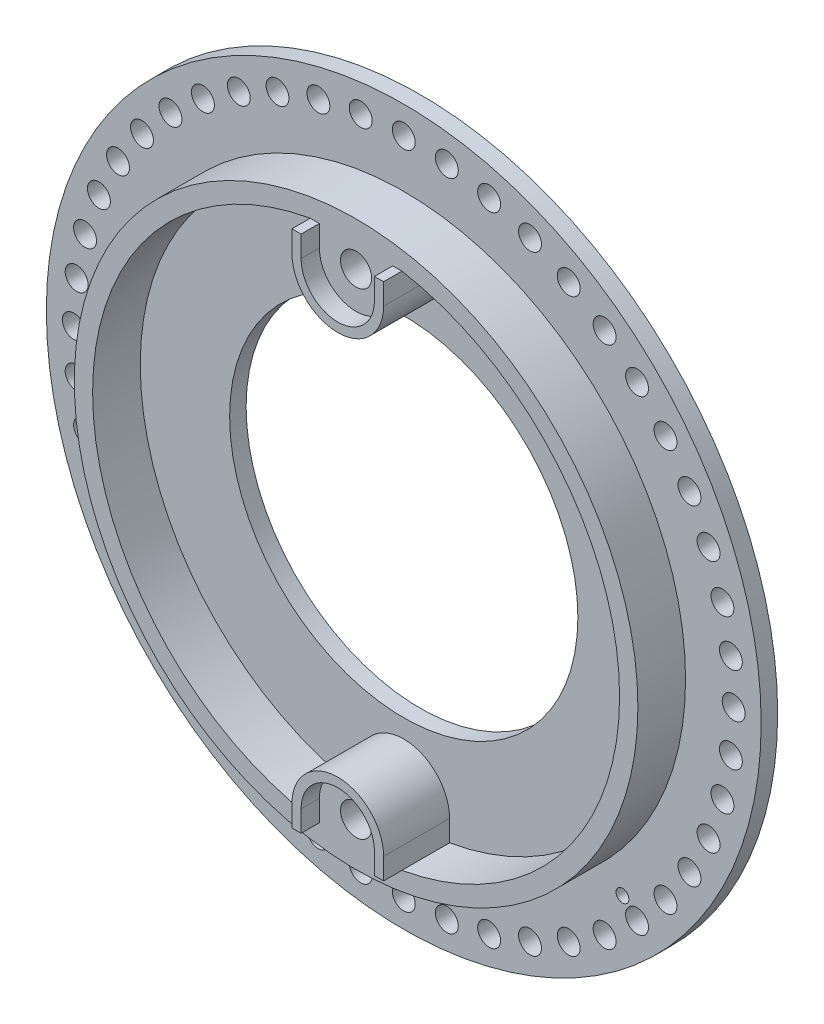
SolidWorks part; units mm, degrees
ref_plane "Front Plane" through (0, 0, 0) normal (0, 0, 1) x (1, 0, 0)
ref_plane "Top Plane" through (0, 0, 0) normal (0, 1, 0) x (1, 0, 0)
ref_plane "Right Plane" through (0, 0, 0) normal (1, 0, 0) x (0, 0, -1)
sketch "Sketch1" plane through (0, 0, 0) normal (0, 0, 1) x (1, 0, 0)
  circle A0 centre (0, 0) radius 39
  dimension "D1" = 78
extrude "Boss-Extrude1" add sketch "Sketch1" along normal blind 1.8
sketch "Sketch3" plane through (0, 0, 1.8) normal (0, 0, 1) x (1, 0, 0)
  line L0 (-5, 26) -> (-5, 28.3119)
  line L1 (5, 26) -> (5, 28.3119)
  line L2 (5, -26) -> (5, -28.3119)
  line L3 (-5, -26) -> (-5, -28.3119)
  circle A0 centre (0, 0) radius 30.75
  arc A1 (-5, 28.3119) -> (-5, -28.3119) centre (0, 0) ccw
  arc A2 (-5, 26) -> (5, 26) centre (0, 26) ccw
  circle A3 centre (0, 0) radius 28.75 construction
  arc A4 (5, -26) -> (-5, -26) centre (0, -26) ccw
  arc A5 (5, -28.3119) -> (5, 28.3119) centre (0, 0) ccw
  point P18 (0, 0)
  point P22 (-0.2453, 0)
  dimension "D1" = 61.5
  dimension "D3" = 10
  dimension "D5" = 2
  dimension "D4" = 26
  dimension "D2" = 2
extrude "Boss-Extrude2" add sketch "Sketch3" along normal blind 5.2 contours A1 L3 A4 L2 A5 L1 A2 L0 | A0
sketch "Sketch5" plane through (0, 0, 7) normal (0, 0, 1) x (1, 0, 0)
  circle A0 centre (0, -26) radius 1.7
  circle A1 centre (0, 26) radius 1.7
  point P7 (0, 0)
  dimension "D1" = 26
  dimension "D2" = 3.4
  dimension "D3" = 2
  dimension "D4" = 52
extrude "Cut-Extrude2" cut sketch "Sketch5" against normal up to surface (7 mm away) up to face at (39, 0, 0)
sketch "Sketch6" plane through (0, 0, 0) normal (0, 0, -1) x (-1, 0, 0)
  circle A0 centre (0, 26) radius 3
  circle A1 centre (0, -26) radius 3
  dimension "D1" = 6
  dimension "D2" = 6
  dimension "D3" = 26
  dimension "D4" = 26
extrude "Cut-Extrude3" cut sketch "Sketch6" against normal blind 4.5
sketch "Sketch7" plane through (0, 0, 0) normal (0, 0, -1) x (-1, 0, 0)
  circle A0 centre (0, 0) radius 19
  dimension "D1" = 38
extrude "Cut-Extrude4" cut sketch "Sketch7" against normal up to surface (1.8 mm away) up to face at (0, 0, 1.8)
sketch "Sketch8" plane through (0, 0, 1.8) normal (0, 0, 1) x (1, 0, 0)
  circle A0 centre (36, 0) radius 1.25
  circle A1 centre (35.692, -4.6989) radius 1.25
  circle A2 centre (34.7733, -9.3175) radius 1.25
  circle A3 centre (33.2597, -13.7766) radius 1.25
  circle A4 centre (31.1769, -18) radius 1.25
  circle A5 centre (28.5607, -21.9154) radius 1.25
  circle A6 centre (25.4558, -25.4558) radius 1.25
  circle A7 centre (21.9154, -28.5607) radius 1.25
  circle A8 centre (18, -31.1769) radius 1.25
  circle A9 centre (13.7766, -33.2597) radius 1.25
  circle A10 centre (9.3175, -34.7733) radius 1.25
  circle A11 centre (4.6989, -35.692) radius 1.25
  circle A12 centre (0, -36) radius 1.25
  circle A13 centre (-4.6989, -35.692) radius 1.25
  circle A14 centre (-9.3175, -34.7733) radius 1.25
  circle A15 centre (-13.7766, -33.2597) radius 1.25
  circle A16 centre (-18, -31.1769) radius 1.25
  circle A17 centre (-21.9154, -28.5607) radius 1.25
  circle A18 centre (-25.4558, -25.4558) radius 1.25
  circle A19 centre (-28.5607, -21.9154) radius 1.25
  circle A20 centre (-31.1769, -18) radius 1.25
  circle A21 centre (-33.2597, -13.7766) radius 1.25
  circle A22 centre (-34.7733, -9.3175) radius 1.25
  circle A23 centre (-35.692, -4.6989) radius 1.25
  circle A24 centre (-36, 0) radius 1.25
  circle A25 centre (-35.692, 4.6989) radius 1.25
  circle A26 centre (-34.7733, 9.3175) radius 1.25
  circle A27 centre (-33.2597, 13.7766) radius 1.25
  circle A28 centre (-31.1769, 18) radius 1.25
  circle A29 centre (-28.5607, 21.9154) radius 1.25
  circle A30 centre (-25.4558, 25.4558) radius 1.25
  circle A31 centre (-21.9154, 28.5607) radius 1.25
  circle A32 centre (-18, 31.1769) radius 1.25
  circle A33 centre (-13.7766, 33.2597) radius 1.25
  circle A34 centre (-9.3175, 34.7733) radius 1.25
  circle A35 centre (-4.6989, 35.692) radius 1.25
  circle A36 centre (0, 36) radius 1.25
  circle A37 centre (4.6989, 35.692) radius 1.25
  circle A38 centre (9.3175, 34.7733) radius 1.25
  circle A39 centre (13.7766, 33.2597) radius 1.25
  circle A40 centre (18, 31.1769) radius 1.25
  circle A41 centre (21.9154, 28.5607) radius 1.25
  circle A42 centre (25.4558, 25.4558) radius 1.25
  circle A43 centre (28.5607, 21.9154) radius 1.25
  circle A44 centre (31.1769, 18) radius 1.25
  circle A45 centre (33.2597, 13.7766) radius 1.25
  circle A46 centre (34.7733, 9.3175) radius 1.25
  circle A47 centre (35.692, 4.6989) radius 1.25
  point P104 (0, 0)
  dimension "D1" = 36
  dimension "D2" = 2.5
  dimension "D3" = 48
extrude "Cut-Extrude5" cut sketch "Sketch8" against normal up to surface (1.8 mm away) up to face at (-19, 0, 0)
fillet "Fillet1" radius 1.5 2 edges at (-3, -26, 4.5) (-3, 26, 4.5)
sketch "Sketch9" plane through (0, 0, 7) normal (0, 0, 1) x (1, 0, 0)
  line L2 (-4, 28.3119) -> (-5, 28.3119)
  line L3 (4, 28.3119) -> (5, 28.3119)
  line L4 (4, 28.3119) -> (4, 26)
  line L5 (-4, 26) -> (-4, 28.3119)
  line L6 (4, 28.3119) -> (4, 26)
  line L7 (-4, 26) -> (-4, 28.3119)
  line L8 (-5, 28.3119) -> (-5, 26)
  line L9 (5, 26) -> (5, 28.3119)
  line L10 (-5, -26) -> (-5, -28.3119)
  line L11 (-4, -28.3119) -> (-5, -28.3119)
  line L12 (-4, -28.3119) -> (-4, -26)
  line L13 (4, -26) -> (4, -28.3119)
  line L14 (4, -28.3119) -> (5, -28.3119)
  line L15 (5, -28.3119) -> (5, -26)
  arc A2 (4, -26) -> (-4, -26) centre (0, -26) ccw
  arc A4 (-5, 26) -> (5, 26) centre (0, 26) ccw
  arc A5 (-4, 26) -> (4, 26) centre (0, 26) ccw
  arc A6 (-4, 26) -> (4, 26) centre (0, 26) ccw
  arc A8 (5, -26) -> (-5, -26) centre (0, -26) ccw
  point P26 (0, 0)
  dimension "D1" = 2
  dimension "D2" = 1
extrude "Boss-Extrude3" add sketch "Sketch9" along normal blind 2
sketch "Alignment_Hole" plane through (0, 0, 0) normal (0, 0, -1) x (-1, 0, 0)
  line L0 (0, 0) -> (-49.8691, 0) construction
  line L1 (-5.6645, -5.6645) -> (-42.6819, -42.6819) construction
  circle A0 centre (-23.8649, -23.8649) radius 0.7
  circle A1 centre (-25.4558, -25.4558) radius 1.25 construction
  dimension "D1" = 1.4
  dimension "D2" = 2.25
  dimension "D3" = 45
extrude "Alignment_Hole - Cut" cut sketch "Alignment_Hole" against normal through all both and the other way through all
equation "\"D2@Sketch6\"=\"D1@Sketch6\""
